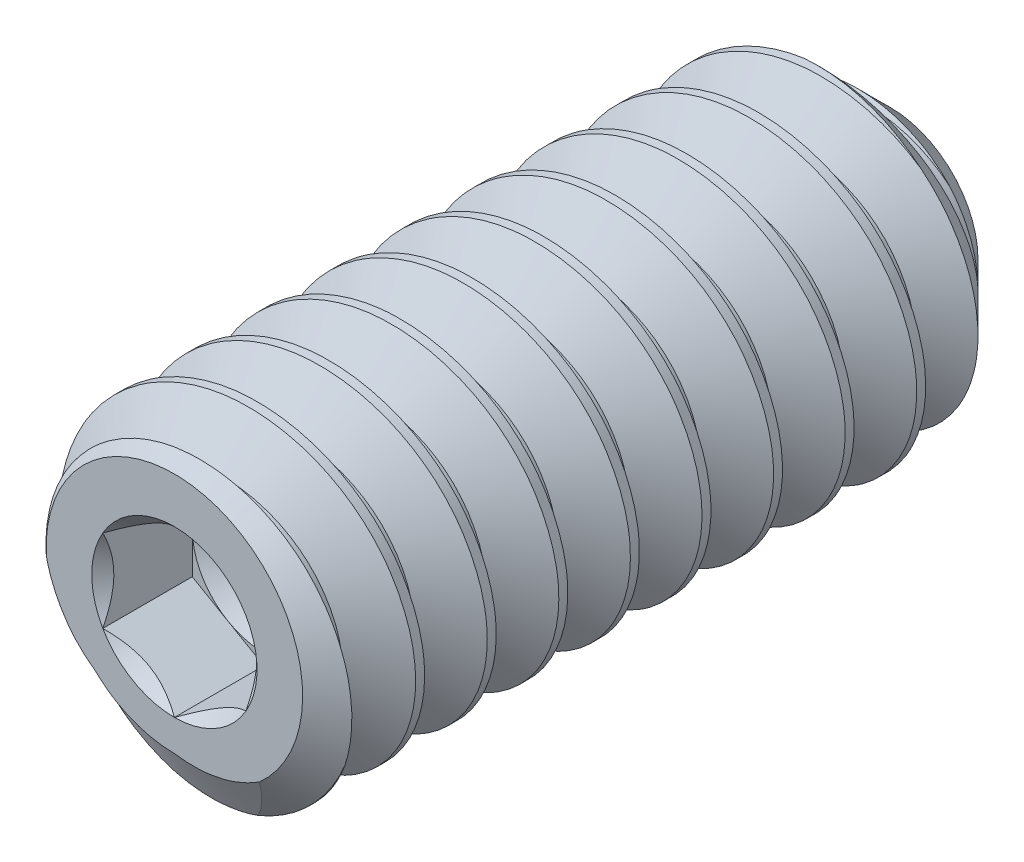
SolidWorks part; units mm, degrees
material "Plain Carbon Steel"
ref_plane "Front" through (0, 0, 0) normal (0, 0, 1) x (1, 0, 0)
ref_plane "Top" through (0, 0, 0) normal (0, 1, 0) x (1, 0, 0)
ref_plane "Right" through (0, 0, 0) normal (1, 0, 0) x (0, 0, -1)
sketch "Sketch22" plane through (0, 0, 0) normal (1, 0, 0) x (0, 0, -1)
  line L0 (-2.9408, 0) -> (-2.9408, 1.1379)
  line L1 (-2.9408, 1.1379) -> (-2.7416, 1.4224)
  line L2 (-2.7416, 1.4224) -> (2.7662, 1.4224)
  line L3 (2.7662, 1.4224) -> (3.4092, 0.7794)
  line L4 (3.4092, 0.7794) -> (2.9408, 0)
  line L5 (2.9408, 0) -> (-2.9408, 0)
  line L6 (2.9408, 0) -> (3.4092, 0) construction
  line L7 (3.4092, 0) -> (3.4092, 0.7794) construction
  line L8 (3.4092, -0.7794) -> (2.9408, 0) construction
  line L9 (-2.7416, -1.4224) -> (2.7662, -1.4224) construction
  dimension "Dia" = 2.8448
  dimension "Length" = 6.35
  dimension "D3" = 35
  dimension "D5" = 118
  dimension "D6" = 45
  dimension "D7" = 2.2758
revolve "Revolve1" add sketch "Sketch22" angle 360 about L6
ref_plane "Plane1" through (0, 0, -3.4092) normal (0, 0, 1) x (1, 0, 0)
sketch "Sketch27" plane through (0, 0, -3.4092) normal (0, 0, 1) x (1, 0, 0)
  circle A0 centre (0, 0) radius 1.4224 construction
  circle A1 centre (0, 0) radius 1.4224
curve "Helix/Spiral1" pitch 0.635 height 6.985 radius 1.4224 centre (0, 0, -3.4092) axis (0, 0, 1) start towards (0, 1, 0)
sketch "Sketch28" plane through (0, 0, 0) normal (1, 0, 0) x (0, 0, -1)
  line L0 (3.4092, 1.4224) -> (3.9648, 1.4224)
  line L1 (3.9648, 1.4224) -> (3.7267, 1.01)
  line L2 (3.7267, 1.01) -> (3.6473, 1.01)
  line L3 (3.6473, 1.01) -> (3.4092, 1.4224)
  line L4 (3.5282, 1.2162) -> (3.8457, 1.2162) construction
  line L6 (-2.7416, 1.4224) -> (2.7662, 1.4224) construction
  line L7 (3.4092, 1.5646) -> (3.4092, -1.5646) construction
  dimension "D1" = 0.0794
  dimension "D3" = 60
  dimension "D2" = 0.3175
sweep "Cut-Sweep2" cut profiles "Sketch28" path "Helix/Spiral1" align with end faces yes
sketch "Sketch23" plane through (0, 0, 2.9408) normal (0, 0, 1) x (1, 0, 0)
  line L1 (0, 0.7332) -> (-0.635, 0.3666)
  line L2 (-0.635, 0.3666) -> (-0.635, -0.3666)
  line L3 (-0.635, -0.3666) -> (0, -0.7332)
  line L4 (0, -0.7332) -> (0.635, -0.3666)
  line L5 (0.635, -0.3666) -> (0.635, 0.3666)
  line L6 (0.635, 0.3666) -> (0, 0.7332)
  circle A0 centre (0, 0) radius 0.635 construction
  dimension "Hex" = 1.27
extrude "Cut-Extrude10" cut sketch "Sketch23" against normal blind 0.7937
sketch "Sketch24" plane through (0, 0, 2.9408) normal (0, 0, 1) x (1, 0, 0)
  circle A0 centre (0, 0) radius 0.7332
extrude "Cut-Extrude11" cut sketch "Sketch24" against normal through all draft 45
sketch "Sketch26" plane through (0, 0, 2.1471) normal (0, 0, 1) x (1, 0, 0)
  circle A0 centre (0, 0) radius 0.635 construction
  circle A1 centre (0, 0) radius 0.635
extrude "Cut-Extrude12" cut sketch "Sketch26" against normal through all draft 60
sketch "Sketch30" plane through (0, 0, 0) normal (1, 0, 0) x (0, 0, -1)
  line L0 (-2.7416, 1.4224) -> (2.7662, 1.4224) construction
  line L1 (-2.9408, 0) -> (-2.9408, 1.1379) construction
  line L2 (3.4092, 0) -> (3.4092, 0.7794) construction
  line L3 (-2.7416, -1.4224) -> (2.7662, -1.4224) construction
  point P0 (-2.9408, 1.4224)
  point P1 (3.4092, 1.4224)
  point P2 (3.4092, -1.4224)
  point P11 (1.8217, -1.4224)
  dimension "D1" = 1.5875
sketch "Sketch31" plane through (0, 0, 0) normal (1, 0, 0) x (0, 0, -1)
  line L2 (2.9408, 0) -> (3.4092, -0.7794)
  line L3 (3.4092, 0.7794) -> (2.9408, 0)
equation "\"D7@Sketch22\"=\"Dia@Sketch22\"*.8"
equation "\"D1@Sketch28\" = \"D4@Helix/Spiral1\" * .125"
equation "\"D3@Helix/Spiral1\" = \"Length@Sketch22\" + \"D4@Helix/Spiral1\""
equation "\"D1@Sketch30\" = \"D4@Helix/Spiral1\" * 2.5"
equation "\"hex Depth@Cut-Extrude10\" = \"Hex@Sketch23\" * .625"
equation "\"D2@Sketch28\" = \"D4@Helix/Spiral1\" * .5"
